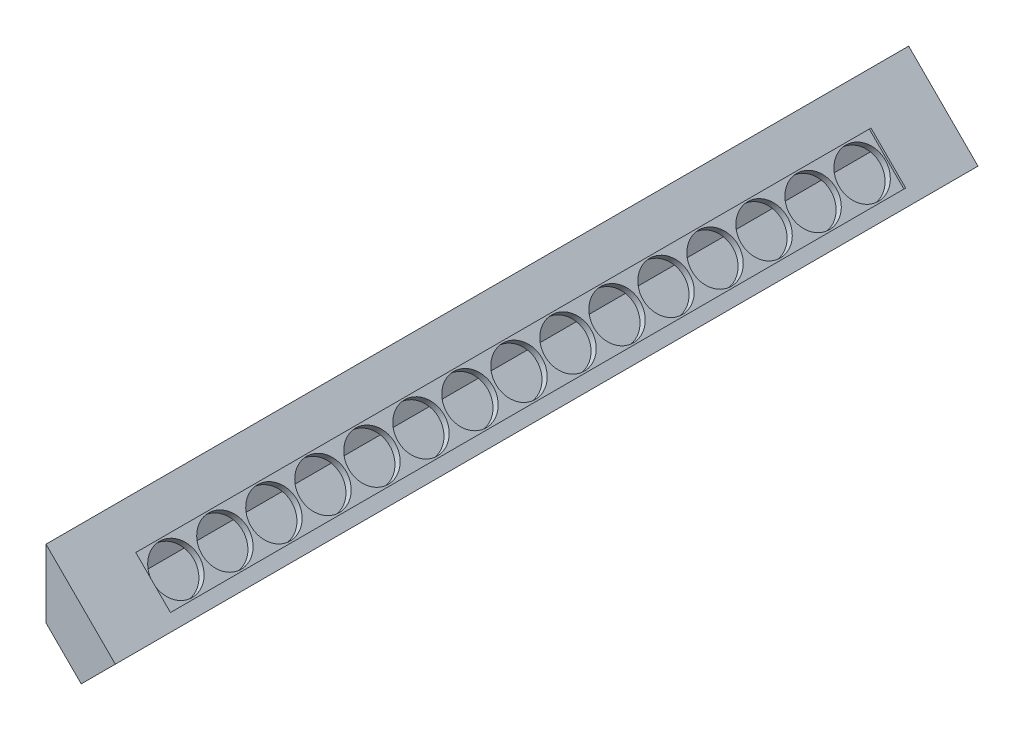
SolidWorks part; units mm, degrees
ref_plane "Front Plane" through (0, 0, 0) normal (0, 0, 1) x (1, 0, 0)
ref_plane "Top Plane" through (0, 0, 0) normal (0, 1, 0) x (1, 0, 0)
ref_plane "Right Plane" through (0, 0, 0) normal (1, 0, 0) x (0, 0, -1)
sketch "Sketch1" plane through (0, 0, 0) normal (0, 0, 1) x (1, 0, 0)
  line L0 (-70.7107, 70.7107) -> (-70.7107, -70.7107)
  line L1 (-70.7107, -70.7107) -> (0, 0)
  line L3 (0, 0) -> (-70.7107, 70.7107)
  dimension "D2" = 100
  dimension "D3" = 100
extrude "Boss-Extrude1" add sketch "Sketch1" along normal blind 880
chamfer "Chamfer1" distance 50.8 angle 90 1 edges at (-70.7107, -70.7107, 440) first distance on face at (-35.3553, -35.3553, 440)
chamfer "Chamfer2" [suppressed] distance 25 angle 90
sketch "Sketch3" plane through (0, 0, 0) normal (0.7071, 0.7071, 0) x (0, 0, -1)
  line L0 (-880, 37.4) -> (0, 37.4) construction
  line L3 (0, 0) -> (0, 100) construction
  line L4 (-815, 12.4) -> (-65, 12.4)
  line L5 (-815, 12.4) -> (-815, 62.4)
  line L6 (-815, 62.4) -> (-65, 62.4)
  line L7 (-65, 12.4) -> (-65, 62.4)
  line L8 (-440, 62.4) -> (-440, 12.4) construction
  line L9 (-815, 37.4) -> (-65, 37.4) construction
  line L10 (-880, 0) -> (-880, 100) construction
  line L11 (-880, 0) -> (0, 0) construction
  point P2 (0, 35.1262)
  point P5 (-889, 34.431)
  point P6 (-440, 37.4)
  dimension "D1" = 50
  dimension "D2" = 750
  dimension "D3" = 37.4
extrude "Cut-Extrude1" cut sketch "Sketch3" against normal blind 2.5
sketch "Sketch4" plane through (-1.7678, -1.7678, 0) normal (0.7071, 0.7071, 0) x (0, 0, -1)
  line L0 (-815, 37.4) -> (-65, 37.4) construction
  line L1 (-815, 62.4) -> (-815, 12.4) construction
  line L2 (-65, 12.4) -> (-65, 62.4) construction
  line L3 (-440, 62.4) -> (-440, 12.4) construction
  line L4 (-65, 62.4) -> (-815, 62.4) construction
  line L5 (-815, 12.4) -> (-65, 12.4) construction
  circle A0 centre (-440, 37.4) radius 23.5
  circle A1 centre (-490, 37.4) radius 23.5
  circle A2 centre (-540, 37.4) radius 23.5
  circle A3 centre (-590, 37.4) radius 23.5
  circle A4 centre (-640, 37.4) radius 23.5
  circle A5 centre (-690, 37.4) radius 23.5
  circle A6 centre (-740, 37.4) radius 23.5
  circle A7 centre (-790, 37.4) radius 23.5
  circle A8 centre (-390, 37.4) radius 23.5
  circle A9 centre (-340, 37.4) radius 23.5
  circle A10 centre (-290, 37.4) radius 23.5
  circle A11 centre (-240, 37.4) radius 23.5
  circle A12 centre (-190, 37.4) radius 23.5
  circle A13 centre (-140, 37.4) radius 23.5
  circle A14 centre (-90, 37.4) radius 23.5
  dimension "D1" = 47
  dimension "D5" = 50
  dimension "D2" = 50
  dimension "D3" = 8
  dimension "D4" = 8
extrude "Cut-Extrude2" cut sketch "Sketch4" against normal blind 11.9
shell "Shell1" thickness 7.5 removed face at (-53.2451, 32.8805, 90) removed face at (-53.2451, 32.8805, 90) removed face at (-53.2451, 32.8805, 140) removed face at (-53.2451, 32.8805, 140) removed face at (-53.2451, 32.8805, 190) removed face at (-53.2451, 32.8805, 190) removed face at (-53.2451, 32.8805, 240) removed face at (-53.2451, 32.8805, 240) removed face at (-53.2451, 32.8805, 290) removed face at (-53.2451, 32.8805, 290) removed face at (-53.2451, 32.8805, 340) removed face at (-53.2451, 32.8805, 340) removed face at (-53.2451, 32.8805, 390) removed face at (-53.2451, 32.8805, 390) removed face at (-53.2451, 32.8805, 440) removed face at (-53.2451, 32.8805, 440) removed face at (-53.2451, 32.8805, 490) removed face at (-53.2451, 32.8805, 490) removed face at (-53.2451, 32.8805, 540) removed face at (-53.2451, 32.8805, 540) removed face at (-53.2451, 32.8805, 590) removed face at (-53.2451, 32.8805, 590) removed face at (-53.2451, 32.8805, 640) removed face at (-53.2451, 32.8805, 640) removed face at (-53.2451, 32.8805, 690) removed face at (-53.2451, 32.8805, 690) removed face at (-53.2451, 32.8805, 740) removed face at (-53.2451, 32.8805, 740) removed face at (-53.2451, 32.8805, 790) removed face at (-53.2451, 32.8805, 790)
